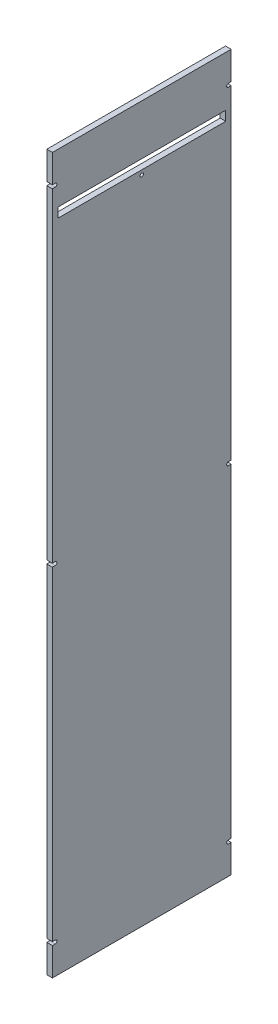
SolidWorks part; units mm, degrees
ref_plane "Front Plane" through (0, 0, 0) normal (0, 0, 1) x (1, 0, 0)
ref_plane "Top Plane" through (0, 0, 0) normal (0, 1, 0) x (1, 0, 0)
ref_plane "Right Plane" through (0, 0, 0) normal (1, 0, 0) x (0, 0, -1)
sketch "Sketch1" plane through (0, 0, 0) normal (0, 1, 0) x (1, 0, 0)
  line L1 (0, 0) -> (4.7625, 0)
  line L2 (0, 0) -> (0, 152.4)
  line L3 (0, 152.4) -> (4.7625, 152.4)
  line L4 (4.7625, 0) -> (4.7625, 152.4)
  dimension "D1" = 152.4
  dimension "D2" = 4.7625
extrude "Boss-Extrude1" add sketch "Sketch1" along normal blind 609.6
sketch "Sketch2" plane through (4.7625, 0, 0) normal (1, 0, 0) x (0, 0, -1)
  line L1 (4.7625, 558.8) -> (147.6375, 558.8)
  line L2 (4.7625, 558.8) -> (4.7625, 566.7375)
  line L3 (4.7625, 566.7375) -> (147.6375, 566.7375)
  line L4 (147.6375, 558.8) -> (147.6375, 566.7375)
extrude "Cut-Extrude1" cut sketch "Sketch2" against normal through all
hole_wizard "#4 Clearance Hole1" positions "Sketch9" profile "Sketch10" hole size "#4" standard "ANSI Inch" end condition through all
sketch "Sketch9" plane through (4.7625, 0, 0) normal (1, 0, 0) x (0, 0, -1)
  line L0 (147.6375, 550.8625) -> (4.7625, 558.8) construction
  line L1 (4.7625, 558.8) -> (147.6375, 558.8) construction
  point P5 (76.2, 554.8313)
sketch "Sketch10" plane through (4.7625, 554.8313, -76.2) normal (0, 1, 0) x (0, 0, -1)
  line L0 (0, 0) -> (0, 4.7625)
  line L1 (0, 4.7625) -> (1.4732, 4.7625)
  line L2 (1.4732, 4.7625) -> (1.4732, 0)
  line L5 (1.4732, 0) -> (0, 0)
  line L11 (0, -6.35) -> (0, 107.95) construction
  dimension "Thru Hole Dia." = 2.9464
  dimension "Thru Hole Depth" = 4.7625
sketch "Sketch12" plane through (4.7625, 0, 0) normal (1, 0, 0) x (0, 0, -1)
  line L0 (150.0188, 0) -> (150.0188, 609.6) construction
  line L1 (0, 0) -> (152.4, 0) construction
  line L2 (0, 609.6) -> (152.4, 609.6) construction
  line L3 (2.3813, 0) -> (2.3813, 609.6) construction
  line L4 (152.4, 609.6) -> (152.4, 0) construction
  line L5 (0, 609.6) -> (0, 0) construction
  line L6 (152.4, 25.4) -> (0, 25.4) construction
  line L7 (150.0188, 23.9395) -> (152.4, 23.9395)
  line L8 (150.0188, 26.8605) -> (152.4, 26.8605)
  line L9 (152.4, 23.9395) -> (152.4, 26.8605)
  line L10 (2.3812, 23.9395) -> (0, 23.9395)
  line L11 (2.3812, 26.8605) -> (0, 26.8605)
  line L12 (0, 23.9395) -> (0, 26.8605)
  line L13 (0, 303.3395) -> (0, 306.2605)
  line L14 (2.3812, 303.3395) -> (0, 303.3395)
  line L15 (2.3812, 306.2605) -> (0, 306.2605)
  line L16 (152.4, 303.3395) -> (152.4, 306.2605)
  line L17 (150.0188, 303.3395) -> (152.4, 303.3395)
  line L18 (150.0188, 306.2605) -> (152.4, 306.2605)
  line L19 (0, 582.7395) -> (0, 585.6605)
  line L20 (2.3812, 582.7395) -> (0, 582.7395)
  line L21 (2.3812, 585.6605) -> (0, 585.6605)
  line L22 (152.4, 582.7395) -> (152.4, 585.6605)
  line L23 (150.0188, 582.7395) -> (152.4, 582.7395)
  line L24 (150.0188, 585.6605) -> (152.4, 585.6605)
  arc A0 (150.0188, 26.8605) -> (150.0188, 23.9395) centre (150.0188, 25.4) ccw
  arc A1 (2.3812, 23.9395) -> (2.3812, 26.8605) centre (2.3812, 25.4) ccw
  arc A2 (2.3812, 303.3395) -> (2.3812, 306.2605) centre (2.3812, 304.8) ccw
  arc A3 (150.0188, 306.2605) -> (150.0188, 303.3395) centre (150.0188, 304.8) ccw
  arc A4 (2.3812, 582.7395) -> (2.3812, 585.6605) centre (2.3812, 584.2) ccw
  arc A5 (150.0188, 585.6605) -> (150.0188, 582.7395) centre (150.0188, 584.2) ccw
  dimension "D4" = 3
  dimension "D1" = 2.3813
  dimension "D2" = 2.3813
  dimension "D3" = 25.4
extrude "Cut-Extrude2" cut sketch "Sketch12" against normal through all
sketch "Sketch13" plane through (4.7625, 0, 0) normal (1, 0, 0) x (0, 0, -1)
  line L0 (4.7625, 566.7375) -> (4.7625, 558.8) construction
  line L1 (147.6375, 566.7375) -> (4.7625, 566.7375) construction
  line L2 (147.6375, 558.8) -> (147.6375, 566.7375) construction
  line L3 (4.7625, 558.8) -> (147.6375, 558.8) construction
  line L4 (4.7625, 566.7375) -> (4.7625, 558.8)
  line L5 (147.6375, 566.7375) -> (4.7625, 566.7375)
  line L6 (147.6375, 558.8) -> (147.6375, 566.7375)
  line L7 (4.7625, 558.8) -> (147.6375, 558.8)
  line L8 (4.6355, 566.8645) -> (4.6355, 558.673)
  line L9 (4.6355, 558.673) -> (147.7645, 558.673)
  line L10 (147.7645, 558.673) -> (147.7645, 566.8645)
  line L11 (147.7645, 566.8645) -> (4.6355, 566.8645)
  dimension "D1" = 0.127
extrude "Cut-Extrude3" cut sketch "Sketch13" against normal through all
